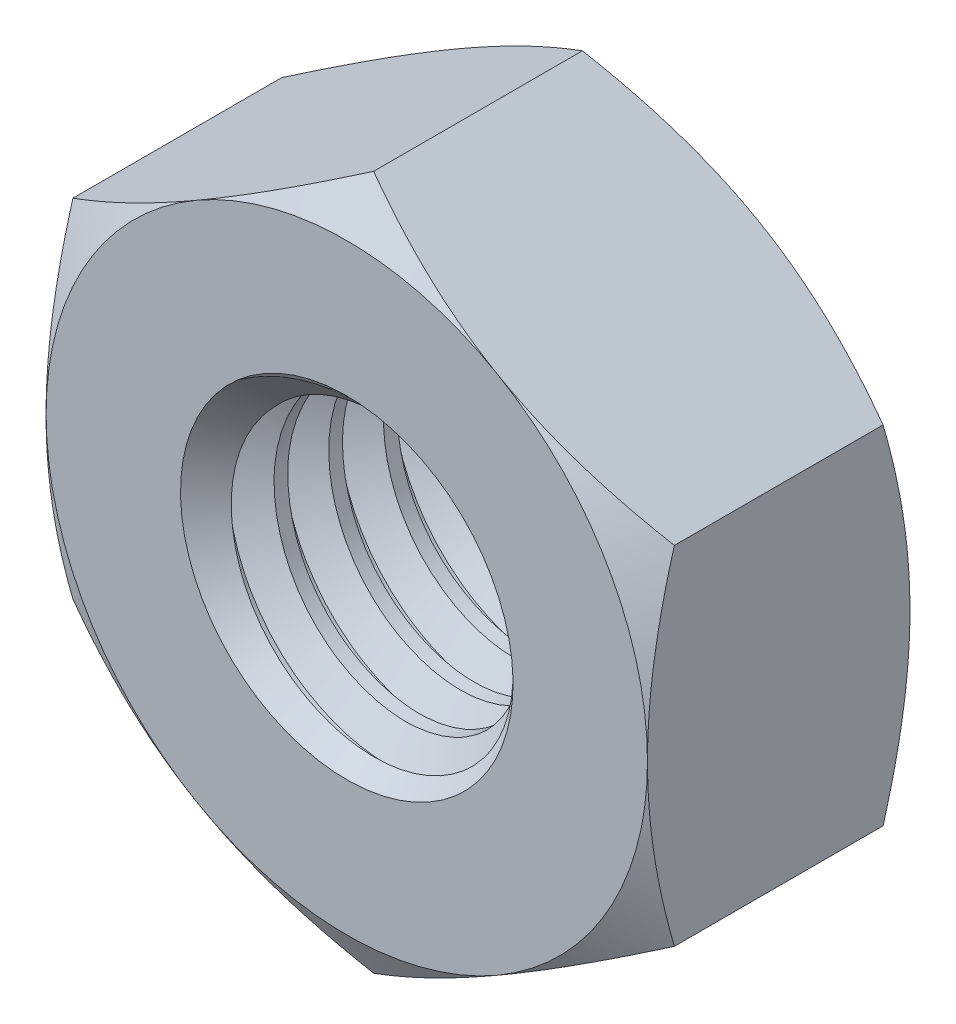
SolidWorks part; units mm, degrees
material "Plain Carbon Steel"
ref_plane "Front Plane" through (0, 0, 0) normal (0, 0, 1) x (1, 0, 0)
ref_plane "Top Plane" through (0, 0, 0) normal (0, 1, 0) x (1, 0, 0)
ref_plane "Right Plane" through (0, 0, 0) normal (1, 0, 0) x (0, 0, -1)
sketch "Sketch2" plane through (0, 0, 0) normal (0, 0, 1) x (1, 0, 0)
  line L0 (2.75, 1.5877) -> (2.75, -1.5877)
  line L1 (-2.75, 1.5877) -> (-2.75, -1.5877)
  line L2 (2.75, 1.5877) -> (0, 3.1754)
  line L3 (0, 3.1754) -> (-2.75, 1.5877)
  line L4 (-2.75, -1.5877) -> (0, -3.1754)
  line L5 (0, -3.1754) -> (2.75, -1.5877)
  circle A0 centre (0, 0) radius 1.25
  dimension "D3" = 2.5
  dimension "D1" = 5.5
  dimension "D2" = 120
  dimension "D4" = 2.75
extrude "Boss-Extrude1" add sketch "Sketch2" along normal mid plane 2.4
sketch "Sketch3" plane through (0, 0, -1.2) normal (0, 0, -1) x (-1, 0, 0)
  line L0 (0, 3.1754) -> (2.75, 1.5877) construction
  line L1 (-2.75, 1.5877) -> (0, 3.1754) construction
  line L2 (-2.75, 1.5877) -> (-2.75, -1.5877) construction
  line L3 (0, -3.1754) -> (-2.75, -1.5877) construction
  line L4 (2.75, -1.5877) -> (0, -3.1754) construction
  line L5 (2.75, 1.5877) -> (2.75, -1.5877) construction
  line L6 (0, 3.1754) -> (2.75, 1.5877) construction
  line L7 (-2.75, 1.5877) -> (0, 3.1754) construction
  line L8 (-2.75, 1.5877) -> (-2.75, -1.5877) construction
  line L9 (0, -3.1754) -> (-2.75, -1.5877) construction
  line L10 (2.75, -1.5877) -> (0, -3.1754) construction
  line L11 (2.75, 1.5877) -> (2.75, -1.5877) construction
  circle A0 centre (0, 0) radius 2.75 construction
sketch "Sketch4" plane through (0, 0, 0) normal (1, 0, 0) x (0, 0, -1)
  line L0 (1.2, -2.75) -> (1.2, 2.75) construction
  line L1 (1.2, -2.75) -> (1.2, 2.75) construction
  line L2 (1.2, 2.75) -> (1.2, 4.3287)
  line L3 (1.2, 4.3287) -> (0.2886, 4.3287)
  line L4 (0.2886, 4.3287) -> (1.2, 2.75)
  line L6 (-2.9945, 0) -> (4.4636, 0) construction
  dimension "D1" = 30
revolve "Cut-Revolve2" cut sketch "Sketch4" angle 360 about L6
mirror "Mirror1" about plane through (0, 0, 0) normal (0, 0, 1) of "Cut-Revolve2"
chamfer "Chamfer1" distance 0.2705 angle 45 2 edges at (1.25, 0, -1.2) (1.25, 0, 1.2)
ref_plane "Plane1" through (0, 0, -1.7) normal (0, 0, -1) x (-1, 0, 0)
sketch "Sketch5" plane through (0, 0, -1.7) normal (0, 0, -1) x (-1, 0, 0)
  circle A0 centre (0, 0) radius 1.25 construction
  circle A1 centre (0, 0) radius 1.25
curve "Helix/Spiral1" pitch 0.5 height 5 radius 1.25 centre (0, 0, -1.7) axis (0, 0, 1) start towards (-1, 0, 0)
sketch "Sketch6" plane through (0, 0, 0) normal (0, 1, 0) x (1, 0, 0)
  line L0 (1.25, 1.7) -> (-1.25, 1.7) construction
  line L1 (1.25, 1.7) -> (-1.25, 1.7) construction
  line L2 (-1.25, 3.2536) -> (-1.25, -1.7335) construction
  line L3 (-1.5205, 1.6687) -> (-1.5205, 1.7312)
  line L4 (-1.5205, 1.7312) -> (-0.9623, 2.0535)
  line L5 (-1.5205, 1.6687) -> (-0.9623, 1.3465)
  line L6 (-0.9623, 2.0535) -> (-0.9623, 1.3465)
  point P9 (-1.5205, 1.7)
  point P11 (-0.9623, 1.7)
  dimension "D1" = 60
  dimension "D2" = 0.0625
  dimension "D3" = 0.2705
sweep "Cut-Sweep1" cut profiles "Sketch6" path "Helix/Spiral1"
